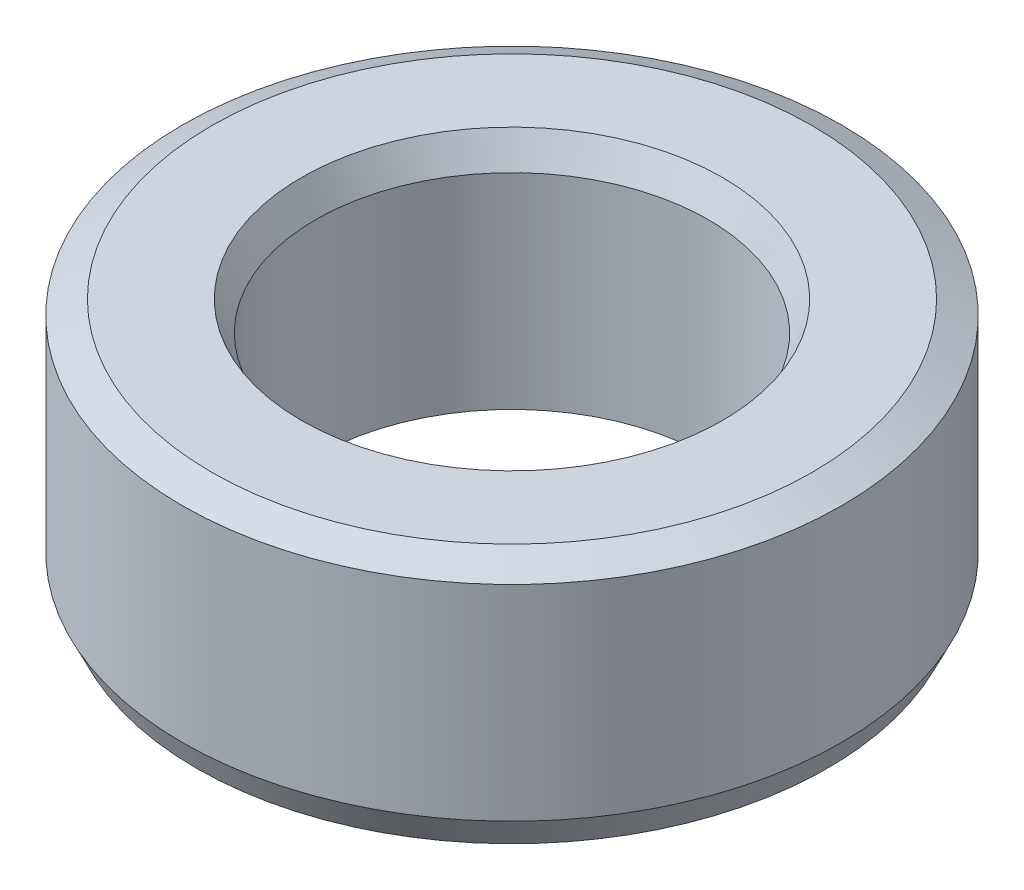
SolidWorks part; units mm, degrees
ref_plane "Front Plane" through (0, 0, 0) normal (0, 0, 1) x (1, 0, 0)
ref_plane "Top Plane" through (0, 0, 0) normal (0, 1, 0) x (1, 0, 0)
ref_plane "Right Plane" through (0, 0, 0) normal (1, 0, 0) x (0, 0, -1)
sketch "Sketch1" plane through (0, 0, 0) normal (0, 1, 0) x (1, 0, 0)
  circle A0 centre (0, 0) radius 50
  dimension "SLEEVE_OD" = 100
extrude "Boss-Extrude1" add sketch "Sketch1" along normal blind 37.7099
sketch "Sketch2" plane through (0, 0, 0) normal (0, 1, 0) x (1, 0, 0)
  circle A0 centre (0, 0) radius 29.7798
  dimension "BORE_D" = 59.5596
extrude "Cut-Extrude1" cut sketch "Sketch2" along normal through all
chamfer "Chamfer1" distance 2.1464 angle 64.33 4 edges at (0, 37.7099, 29.7798) (0, 0, 29.7798) (0, 0, 50) (0, 37.7099, 50) first distance on face at (0, 37.7099, 29.7798) first distance on face at (0, 0, 29.7798) first distance on face at (0, 37.7099, 50)
